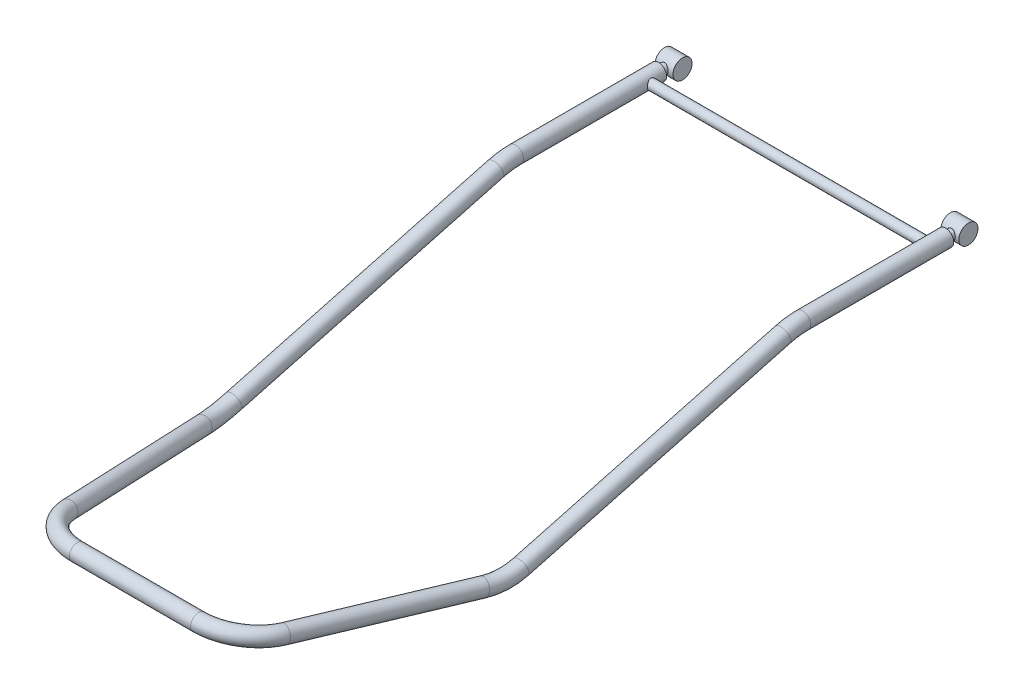
SolidWorks part; units mm, degrees
ref_plane "Front Plane" through (0, 0, 0) normal (0, 0, 1) x (1, 0, 0)
ref_plane "Top Plane" through (0, 0, 0) normal (0, 1, 0) x (1, 0, 0)
ref_plane "Right Plane" through (0, 0, 0) normal (1, 0, 0) x (0, 0, -1)
sketch "Sketch1" plane through (0, 0, 0) normal (1, 0, 0) x (0, 0, -1)
  line L0 (0, 0) -> (-222.25, 0) construction
  line L1 (-222.25, 0) -> (-605.6018, -102.7188) construction
  line L2 (-605.6018, -102.7188) -> (-900.3774, -56.0309) construction
  dimension "D1" = 222.25
  dimension "D2" = 165
  dimension "D3" = 396.875
  dimension "D4" = 156
  dimension "D5" = 298.45
sketch3d "3DSketch1"
  line L0 (0, 0, 0) -> (0, 0, 222.25) construction
  line L1 (0, 0, 222.25) -> (0, -102.7188, 605.6018) construction
  line L2 (0, -102.7188, 605.6018) -> (0, -56.0309, 900.3774) construction
  line L3 (0, 0, 0) -> (0, 0, 222.25) construction
  line L4 (0, 0, 222.25) -> (0, -102.7188, 605.6018) construction
  line L5 (0, -102.7188, 605.6018) -> (0, -56.0309, 900.3774) construction
  line L6 (0, 0, 0) -> (190.5, 0, 0) construction
  line L7 (190.5, 0, 0) -> (190.5, 0, 19.05)
  line L8 (190.5, 0, 19.05) -> (190.5, 0, 208.8741)
  line L9 (0, 0, 222.25) -> (190.5, 0, 222.25) construction
  line L10 (190.5, -3.4619, 235.1701) -> (190.5, -96.5902, 582.7295)
  line L11 (190.5, -102.7188, 605.6018) -> (0, -102.7188, 605.6018) construction
  line L12 (0, -56.0309, 900.3774) -> (80.4355, -56.0309, 900.3774)
  line L13 (142.7827, -64.0803, 849.5558) -> (186.0084, -99.0818, 628.5649)
  line L14 (179.832, 0, 19.05) -> (201.168, 0, 19.05) construction
  line L15 (201.168, 0, 19.05) -> (201.168, 0, 222.25) construction
  line L16 (201.168, 0, 222.25) -> (190.5, 0, 222.25) construction
  line L17 (179.832, 0, 19.05) -> (179.832, 0, 222.25) construction
  line L18 (190.5, 0, 38.1) -> (0, 0, 38.1)
  line L19 (201.6125, 0, 0) -> (177.8, 0, 0)
  arc A0 (186.0084, -99.0818, 628.5649) -> (190.5, -96.5902, 582.7295) centre (146.9094, -7.9436, 606.4822) ccw
  arc A1 (190.5, 0, 208.8741) -> (190.5, -3.4619, 235.1701) centre (190.5, -101.6, 208.8741) ccw
  arc A2 (80.4355, -56.0309, 900.3774) -> (142.7827, -64.0803, 849.5558) centre (80.4355, -65.9645, 837.6592) ccw
  point P6 (190.5, 0, 38.1)
  point P12 (190.5, 0, 19.05)
  point P19 (190.5, -102.7188, 605.6018)
  point P21 (238.6831, 34.1617, 617.7643)
  point P24 (190.5, 0, 222.25)
  point P26 (292.1, -101.6, 208.8741)
  point P29 (132.842, -56.0309, 900.3774)
  point P30 (80.4355, -3.2463, 827.7256)
  point P33 (190.5, 0, 0)
  dimension "D3" = 21.336
  dimension "D7" = 101.6
  dimension "D8" = 63.5
  dimension "D1" = 222.25
  dimension "D2" = 19.05
  dimension "D4" = 38.1
  dimension "D6" = 132.842
  dimension "D9" = 23.8125
  dimension "D10" = 12.7
  dimension "D5" = 177.8
sweep "Main Frame" add path "3DSketch1" circular profile diameter 21.336 parameters "D3"=21.336
sweep "Cross Bar Bottom" add path "3DSketch1<3>" circular profile diameter 12.7 parameters "D3"=12.7
sketch3d "3DSketch1<3>" same geometry as "3DSketch1"
sweep "Swivel Connection" add path "3DSketch1<4>" circular profile diameter 12.7 parameters "D3"=12.7
sketch3d "3DSketch1<4>" same geometry as "3DSketch1"
sweep "Swivel Outer" add path "3DSketch1<5>" circular profile diameter 25.4 parameters "D3"=25.4
sketch3d "3DSketch1<5>" same geometry as "3DSketch1"
mirror "Mirror1" about plane through (0, 0, 0) normal (1, 0, 0) of "Main Frame", "Cross Bar Bottom", "Swivel Connection", "Swivel Outer"
equation "\"bar_dia\"= 0.84in"
equation "\"thin_bar_dia\"= 0.5in"
equation "\"D3@3DSketch1\"=\"bar_dia\""
equation "\"main_fillet\"= 4in"
equation "\"top_fillet\"= 2.5in"
equation "\"D8@3DSketch1\"=\"top_fillet\""
equation "\"D7@3DSketch1\"=\"main_fillet\""
equation "\"D3@Main Frame\"=\"bar_dia\""
equation "\"D3@Cross Bar Bottom\"=\"thin_bar_dia\""
equation "\"D3@Swivel Connection\"=\"thin_bar_dia\""
equation "\"D5@3DSketch1\"=14/2"
equation "\"swivel_major_dia\"= 1in"
equation "\"D3@Swivel Outer\"=\"swivel_major_dia\""
